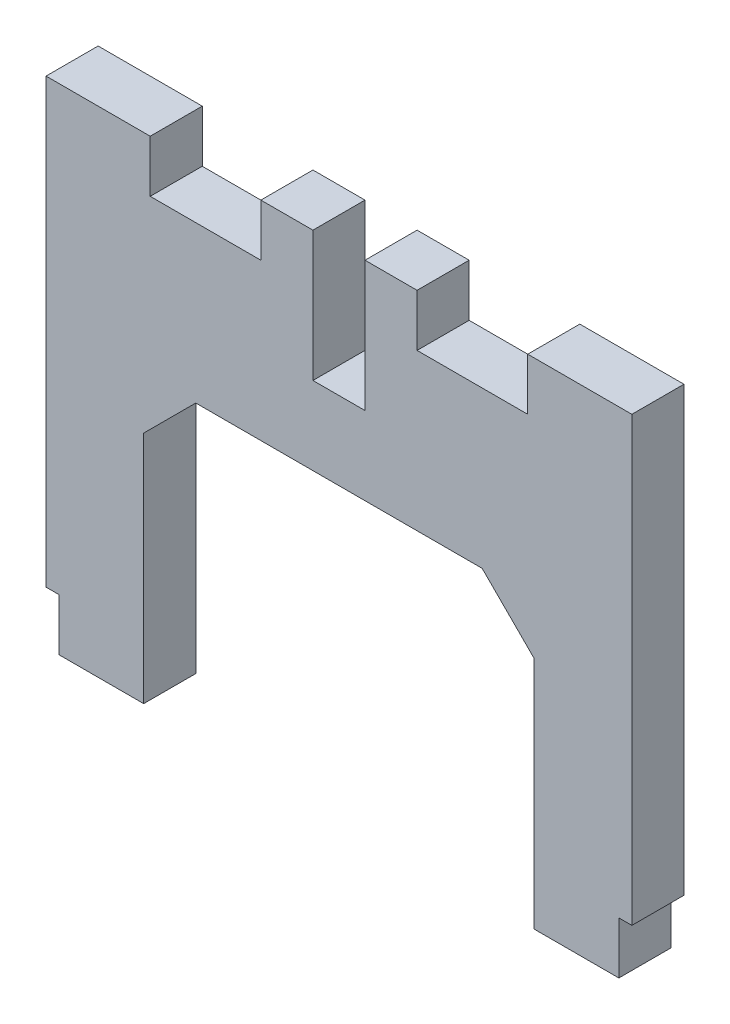
SolidWorks part; units mm, degrees
ref_plane "Front Plane" through (0, 0, 0) normal (0, 0, 1) x (1, 0, 0)
ref_plane "Top Plane" through (0, 0, 0) normal (0, 1, 0) x (1, 0, 0)
ref_plane "Right Plane" through (0, 0, 0) normal (1, 0, 0) x (0, 0, -1)
sketch "Sketch1" plane through (0, 0, 0) normal (0, 0, 1) x (1, 0, 0)
  line L0 (0, 0) -> (0, 30)
  line L1 (0, 30) -> (-20.5, 30)
  line L2 (-20.5, 30) -> (-20.5, 24)
  line L3 (-20.5, 24) -> (-22.5, 24)
  line L9 (-22.5, 18) -> (-7.5, 18)
  line L10 (-7.5, 18) -> (-7.5, -4)
  line L11 (-7.5, -4) -> (-1, -4)
  line L12 (-1, -4) -> (-1, 0)
  line L13 (-1, 0) -> (0, 0)
  line L14 (-22.5, 24) -> (-22.5, 18)
  point P13 (-21.5, 24)
  point P17 (-20.5, 27)
  dimension "D1" = 1
  dimension "D2" = 6.5
  dimension "D3" = 4
  dimension "D4" = 24
  dimension "D5" = 30
  dimension "D6" = 12
  dimension "D7" = 22.5
  dimension "D9" = 20.5
extrude "Boss-Extrude1" add sketch "Sketch1" along normal blind 4
chamfer "Chamfer2" distance 4 angle 45 1 edges at (-7.5, 18, 2)
mirror "Mirror1" about plane through (-22.5, 24, 4) normal (1, 0, 0) of "Chamfer2", "Boss-Extrude1"
sketch "Sketch2" plane through (0, 0, 4) normal (0, 0, 1) x (1, 0, 0)
  line L1 (-24.5, 30) -> (-28.5, 30)
  line L2 (-24.5, 30) -> (-24.5, 34)
  line L3 (-24.5, 34) -> (-28.5, 34)
  line L4 (-28.5, 30) -> (-28.5, 34)
  line L5 (-20.5, 30) -> (-16.5, 30)
  line L6 (-20.5, 30) -> (-20.5, 34)
  line L7 (-20.5, 34) -> (-16.5, 34)
  line L8 (-16.5, 30) -> (-16.5, 34)
  line L9 (0, 30) -> (-8, 30)
  line L10 (0, 30) -> (0, 34)
  line L11 (0, 34) -> (-8, 34)
  line L12 (-8, 30) -> (-8, 34)
  line L13 (-45, 30) -> (-37, 30)
  line L14 (-45, 30) -> (-45, 34)
  line L15 (-45, 34) -> (-37, 34)
  line L16 (-37, 30) -> (-37, 34)
  dimension "D1" = 4
  dimension "D2" = 4
  dimension "D3" = 4
  dimension "D4" = 8
  dimension "D5" = 8
extrude "Boss-Extrude2" add sketch "Sketch2" against normal up to surface (4 mm away) up to face at (-22.5, 12, 0)
